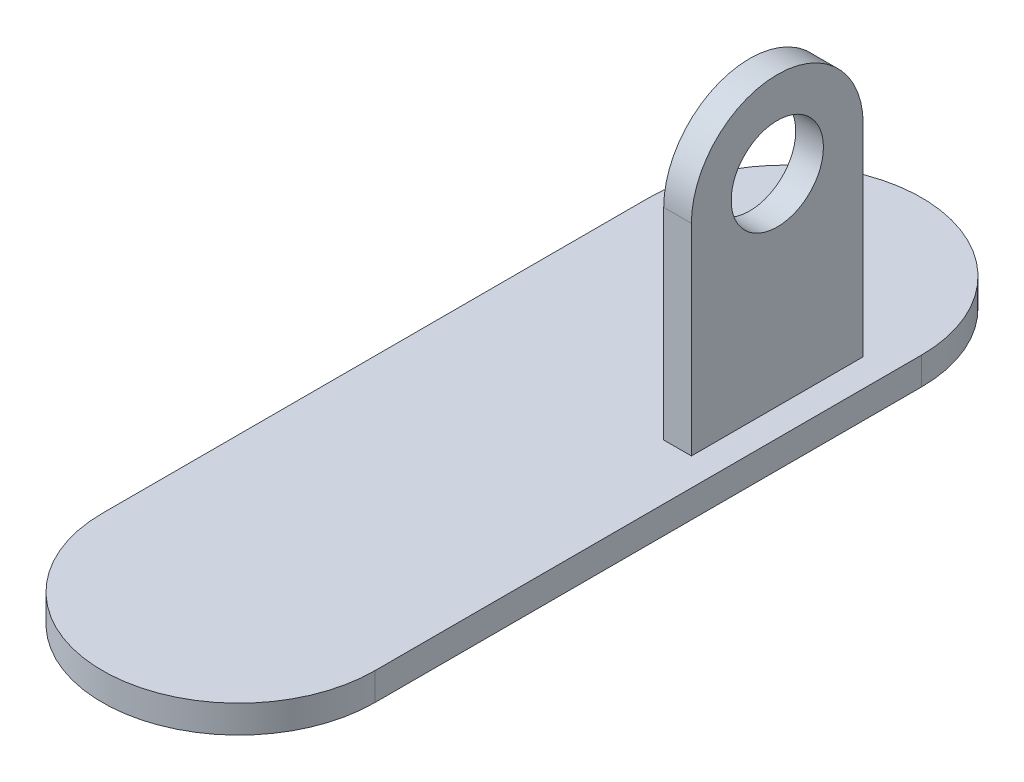
SolidWorks part; units mm, degrees
ref_plane "Front Plane" through (0, 0, 0) normal (0, 0, 1) x (1, 0, 0)
ref_plane "Top Plane" through (0, 0, 0) normal (0, 1, 0) x (1, 0, 0)
ref_plane "Right Plane" through (0, 0, 0) normal (1, 0, 0) x (0, 0, -1)
sketch "Sketch1" plane through (0, 0, 0) normal (0, 1, 0) x (1, 0, 0)
  line L0 (0, -88.9) -> (0, 88.9) construction
  line L2 (44.323, 88.9) -> (44.323, -88.9)
  line L3 (0, 0) -> (-26.323, 0) construction
  line L14 (-44.323, 88.9) -> (-44.323, -88.9)
  arc A0 (44.323, 88.9) -> (-44.323, 88.9) centre (0, 88.9) ccw
  arc A1 (-44.323, -88.9) -> (44.323, -88.9) centre (0, -88.9) ccw
  point P8 (0, 0)
  point P13 (-89.4761, 0)
  point P18 (-35.323, 0)
  dimension "D2" = 88.646
  dimension "D1" = 177.8
extrude "Boss-Extrude1" add sketch "Sketch1" along normal blind 9
sketch "Sketch2" plane through (0, 9, 0) normal (0, 1, 0) x (1, 0, 0)
  line L1 (26.323, 78.9) -> (35.323, 78.9)
  line L2 (26.323, 78.9) -> (26.323, 23.02)
  line L3 (26.323, 23.02) -> (35.323, 23.02)
  line L4 (35.323, 78.9) -> (35.323, 23.02)
  line L5 (-44.323, 88.9) -> (44.323, 88.9) construction
  line L6 (44.323, -88.9) -> (44.323, 88.9) construction
  dimension "D1" = 9
  dimension "D2" = 9
  dimension "D3" = 55.88
  dimension "D4" = 10
extrude "Boss-Extrude2" add sketch "Sketch2" along normal blind 65.53
sketch "Sketch3" plane through (35.323, 0, 0) normal (1, 0, 0) x (0, 0, -1)
  line L0 (23.02, 74.53) -> (78.9, 74.53) construction
  circle A0 centre (50.96, 74.53) radius 27.94
extrude "Boss-Extrude3" add sketch "Sketch3" against normal up to surface (9 mm away) up to face at (26.323, 41.765, -50.96)
sketch "Sketch4" plane through (35.323, 0, 0) normal (1, 0, 0) x (0, 0, -1)
  circle A0 centre (50.96, 74.53) radius 15
  dimension "D1" = 30
extrude "Cut-Extrude1" cut sketch "Sketch4" against normal through all
